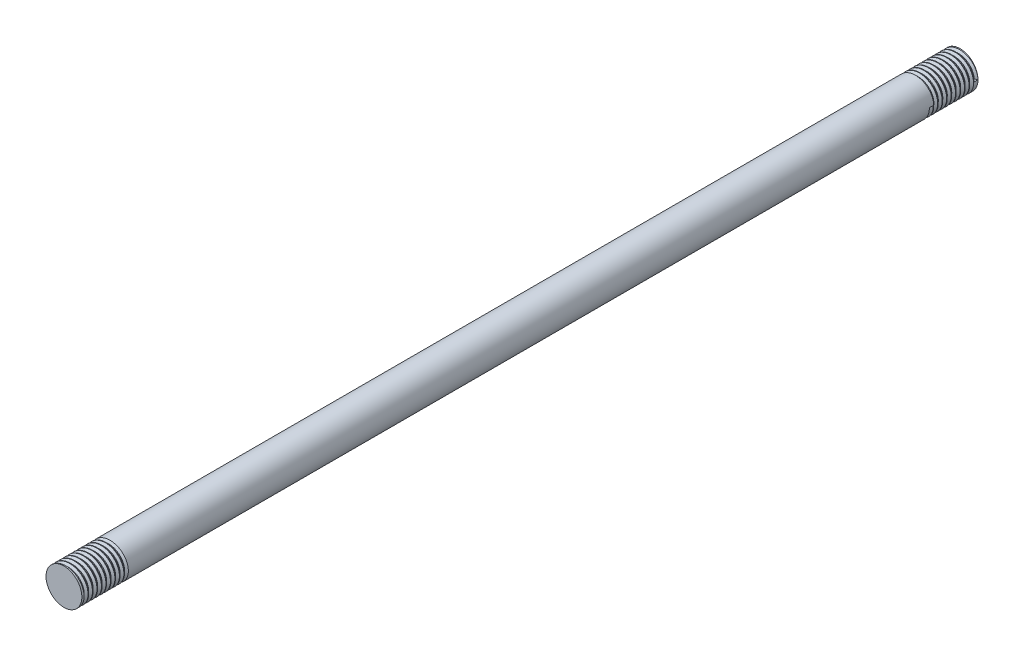
SolidWorks part; units mm, degrees
material "AISI 304"
ref_plane "Front Plane" through (0, 0, 0) normal (0, 0, 1) x (1, 0, 0)
ref_plane "Top Plane" through (0, 0, 0) normal (0, 1, 0) x (1, 0, 0)
ref_plane "Right Plane" through (0, 0, 0) normal (1, 0, 0) x (0, 0, -1)
sketch "Sketch1" plane through (0, 0, 0) normal (0, 0, 1) x (1, 0, 0)
  circle A0 centre (0, 0) radius 4
extrude "Boss-Extrude1" add sketch "Sketch1" along normal blind 200
thread "Thread1" pitch 1 method cut profile "Thread Profile1" start angle 0, offset 0, length 10, pitch 1, diameter 8
ref_plane "Plane1" through (-4, 0, 200) normal (0, -1, 0) x (-1, 0, 0)
sketch "Thread Profile1" plane through (-4, 0, 200) normal (0, -1, 0) x (-1, 0, 0)
  line L0 (0, 0) -> (0, 1) construction
  line L11 (0, 0) -> (0, 0.875)
  line L12 (0, 0.875) -> (-0.5413, 0.5625)
  line L13 (-0.5413, 0.5625) -> (-0.5413, 0.3125)
  line L15 (-0.5413, 0.3125) -> (0, 0)
  line L17 (-0.5413, 0.4375) -> (0, 0.4375) construction
  point P2 (0, 0)
  dimension "Pitch" = 1
  dimension "Profile_Angle" = 60
  dimension "Profile_Land" = 0.25
  dimension "Profile_Height" = 0.5413
thread "Thread2" pitch 1 method cut profile "Thread Profile2" start angle 0, offset 0, length 10, pitch 1, diameter 8
ref_plane "Plane2" through (4, 0, 0) normal (0, -1, 0) x (1, 0, 0)
sketch "Thread Profile2" plane through (4, 0, 0) normal (0, -1, 0) x (1, 0, 0)
  line L0 (0, 0) -> (0, 1) construction
  line L11 (0, 0) -> (0, 0.875)
  line L12 (0, 0.875) -> (-0.5413, 0.5625)
  line L13 (-0.5413, 0.5625) -> (-0.5413, 0.3125)
  line L15 (-0.5413, 0.3125) -> (0, 0)
  line L17 (-0.5413, 0.4375) -> (0, 0.4375) construction
  point P2 (0, 0)
  dimension "Pitch" = 1
  dimension "Profile_Angle" = 60
  dimension "Profile_Land" = 0.25
  dimension "Profile_Height" = 0.5413
